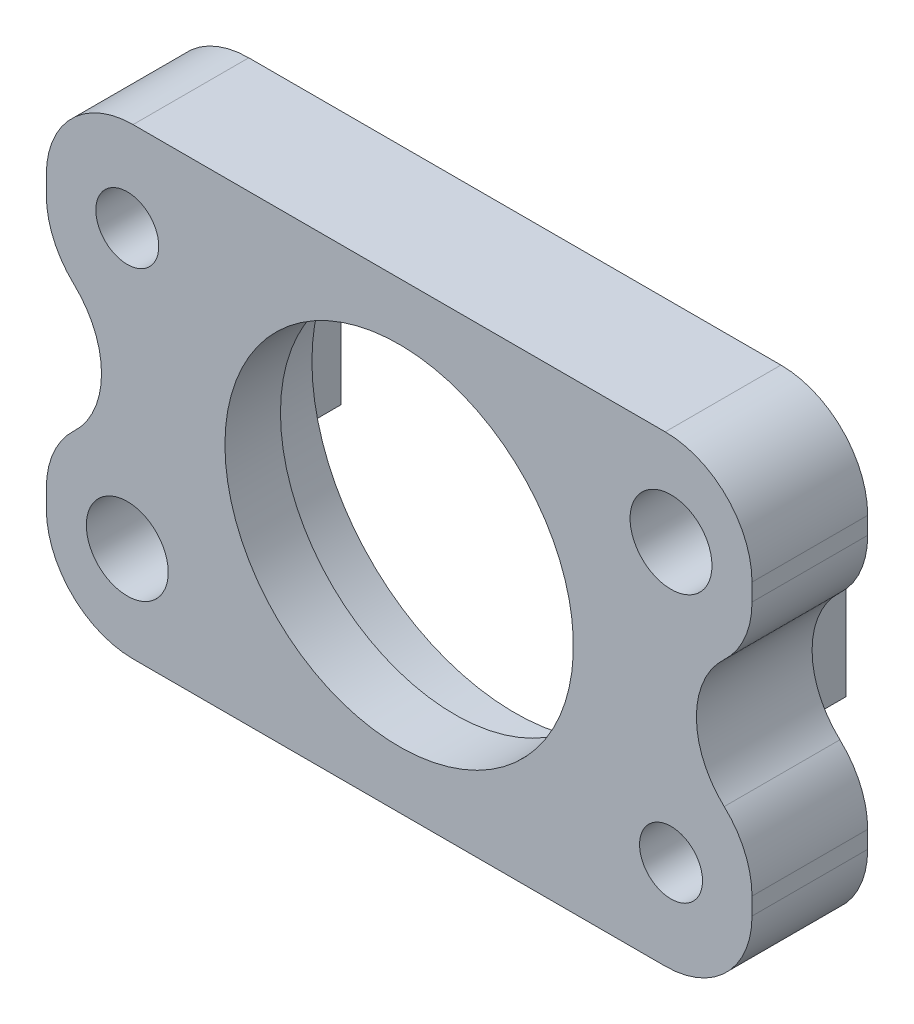
SolidWorks part; units mm, degrees
material "6061 Alloy"
ref_plane "Front Plane" through (0, 0, 0) normal (0, 0, 1) x (1, 0, 0)
ref_plane "Top Plane" through (0, 0, 0) normal (0, 1, 0) x (1, 0, 0)
ref_plane "Right Plane" through (0, 0, 0) normal (1, 0, 0) x (0, 0, -1)
ref_plane "Plane1" through (0, 0, 6.35) normal (0, 0, 1) x (1, 0, 0)
sketch "Sketch1" plane through (0, 0, 6.35) normal (0, 0, 1) x (1, 0, 0)
  line L0 (-254, 12.7) -> (-215.265, 12.7)
  line L1 (-215.265, 12.7) -> (-215.265, 38.1)
  line L2 (-215.265, 38.1) -> (-254, 38.1)
  line L3 (-254, 38.1) -> (-254, 12.7)
  dimension "D1" = 38.735
  dimension "D2" = 25.4
extrude "Boss-Extrude1" add sketch "Sketch1" against normal blind 6.35
sketch "Sketch2" plane through (0, 0, 0) normal (0, 0, -1) x (-1, 0, 0)
  line L0 (215.265, 32.3882) -> (215.265, 18.4118)
  line L1 (254, 38.1) -> (254, 12.7) construction
  line L2 (215.265, 38.1) -> (254, 38.1) construction
  arc A0 (215.265, 18.4118) -> (216.7914, 21.9059) centre (220.0275, 18.4118) cw
  arc A1 (216.7914, 21.9059) -> (216.7914, 28.8941) centre (213.5552, 25.4) ccw
  arc A2 (216.7914, 28.8941) -> (215.265, 32.3882) centre (220.0275, 32.3882) cw
  dimension "D1" = 4.7625
  dimension "D2" = 4.7625
  dimension "D3" = 33.9725
  dimension "D4" = 37.2086
  dimension "D5" = 5.7118
extrude "Cut-Extrude1" cut sketch "Sketch2" against normal through all
sketch "Sketch3" plane through (0, 0, 0) normal (0, 0, -1) x (-1, 0, 0)
  line L0 (254, 20.955) -> (254, 29.845)
  line L1 (215.265, 32.3882) -> (215.265, 38.1) construction
  arc A0 (254, 29.845) -> (254, 20.955) centre (255.7449, 25.4) ccw
  dimension "D1" = 4.7752
  dimension "D2" = 38.735
  dimension "D3" = 40.4799
  dimension "D4" = 8.255
extrude "Cut-Extrude2" cut sketch "Sketch3" against normal through all
sketch "Sketch4" plane through (0, 0, 0) normal (0, 0, -1) x (-1, 0, 0)
  line L0 (221.9071, 20.955) -> (219.6211, 20.955)
  line L1 (219.6211, 20.955) -> (219.6211, 29.845)
  line L2 (219.6211, 29.845) -> (221.9071, 29.845)
  line L3 (221.9071, 29.845) -> (221.9071, 20.955)
  line L4 (254, 38.1) -> (254, 29.845) construction
  line L5 (215.265, 38.1) -> (254, 38.1) construction
  dimension "D1" = 32.0929
  dimension "D2" = 34.3789
  dimension "D3" = 8.255
  dimension "D4" = 17.145
extrude "Boss-Extrude2" add sketch "Sketch4" along normal blind 3.175
sketch "Sketch5" plane through (0, 0, 0) normal (0, 0, -1) x (-1, 0, 0)
  line L0 (249.6439, 20.955) -> (247.3579, 20.955)
  line L1 (247.3579, 20.955) -> (247.3579, 29.845)
  line L2 (247.3579, 29.845) -> (249.6439, 29.845)
  line L3 (249.6439, 29.845) -> (249.6439, 20.955)
  line L4 (254, 38.1) -> (254, 29.845) construction
  line L5 (215.265, 38.1) -> (254, 38.1) construction
  dimension "D1" = 4.3561
  dimension "D2" = 6.6421
  dimension "D3" = 8.255
  dimension "D4" = 17.145
extrude "Boss-Extrude3" add sketch "Sketch5" along normal blind 3.175
hole_wizard "Hole1" positions "Sketch7" profile "Sketch6" legacy
sketch "Sketch7" plane through (0, 0, 0) normal (0, 0, -1) x (-1, 0, 0)
  point P0 (234.6325, 25.4)
sketch "Sketch6" plane through (-234.6325, 25.4, 0) normal (1, 0, 0) x (0, 1, 0)
  line L0 (0, 0) -> (0, 6.35)
  line L1 (0, 6.35) -> (9.5631, 6.35)
  line L2 (9.5631, 6.35) -> (9.5631, 3.302)
  line L3 (9.5631, 3.302) -> (11.1379, 3.302)
  line L4 (11.1379, 3.302) -> (11.1379, 0)
  line L5 (11.1379, 0) -> (0, 0)
  line L6 (0, 110) -> (0, -10) construction
  dimension "Diameter" = 19.1262
  dimension "Depth" = 6.35
  dimension "C-Bore Diameter" = 22.2758
  dimension "C-Bore Depth" = 3.302
hole_wizard "#16 (0.177) Diameter Hole1" positions "Sketch9" profile "Sketch8" hole size "#16" standard "ANSI Inch"
sketch "Sketch9" plane through (0, 0, 6.35) normal (0, 0, 1) x (1, 0, 0)
  point P0 (-249.555, 17.78)
  point P1 (-219.71, 33.02)
sketch "Sketch8" plane through (-249.555, 17.78, 6.35) normal (1, 0, 0) x (0, -1, 0)
  line L0 (0, 0) -> (0, 9.525)
  line L1 (0, 9.525) -> (2.2479, 9.525)
  line L2 (2.2479, 9.525) -> (2.2479, 0)
  line L5 (2.2479, 0) -> (0, 0)
  line L11 (0, -6.35) -> (0, 107.95) construction
  dimension "Thru Hole Dia." = 4.4958
  dimension "Thru Hole Depth" = 9.525
hole_wizard "#29 (0.136) Diameter Hole1" positions "Sketch11" profile "Sketch10" hole size "#29" standard "ANSI Inch"
sketch "Sketch11" plane through (0, 0, 6.35) normal (0, 0, 1) x (1, 0, 0)
  point P0 (-219.71, 17.78)
  point P1 (-249.555, 33.02)
sketch "Sketch10" plane through (-219.71, 17.78, 6.35) normal (1, 0, 0) x (0, -1, 0)
  line L0 (0, 0) -> (0, 9.525)
  line L1 (0, 9.525) -> (1.7272, 9.525)
  line L2 (1.7272, 9.525) -> (1.7272, 0)
  line L5 (1.7272, 0) -> (0, 0)
  line L11 (0, -6.35) -> (0, 107.95) construction
  dimension "Thru Hole Dia." = 3.4544
  dimension "Thru Hole Depth" = 9.525
fillet "Fillet1" radius 4.7625 6 edges at (-254, 20.955, 3.175) (-254, 29.845, 3.175) (-215.265, 12.7, 3.175) (-254, 12.7, 3.175) (-215.265, 38.1, 3.175) (-254, 38.1, 3.175) tangent propagation no
